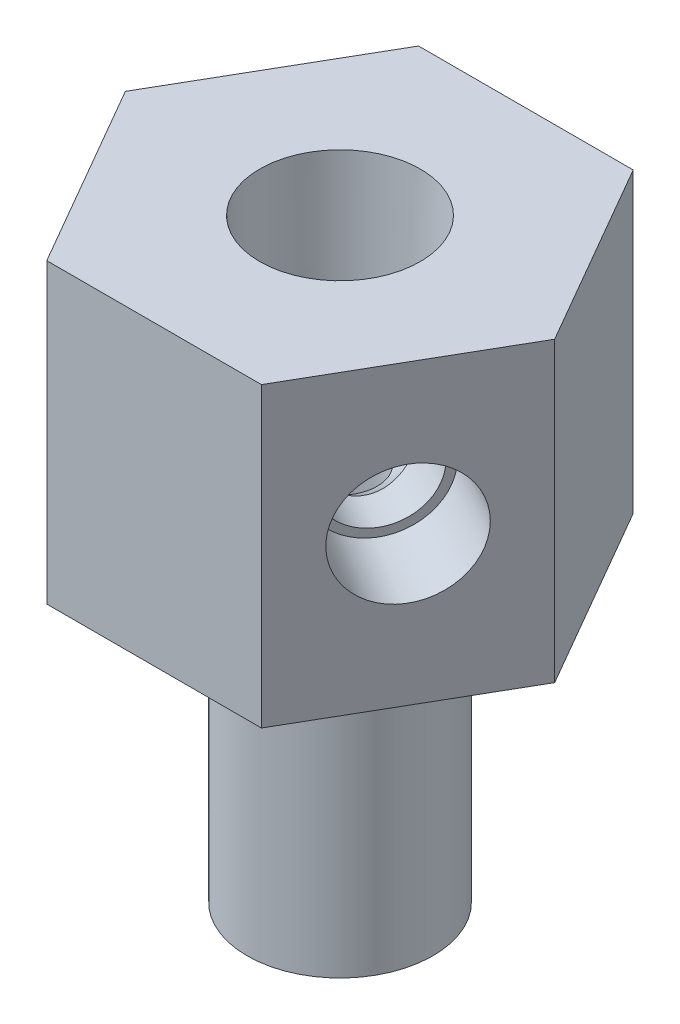
SolidWorks part; units mm, degrees
ref_plane "Front Plane" through (0, 0, 0) normal (0, 0, 1) x (1, 0, 0)
ref_plane "Top Plane" through (0, 0, 0) normal (0, 1, 0) x (1, 0, 0)
ref_plane "Right Plane" through (0, 0, 0) normal (1, 0, 0) x (0, 0, -1)
sketch "Sketch1" plane through (0, 0, 0) normal (0, 1, 0) x (1, 0, 0)
  circle A0 centre (0, 0) radius 7.9375
  dimension "D1" = 15.875
extrude "Boss-Extrude1" add sketch "Sketch1" along normal blind 25.4
cosmetic thread "Cosmetic Thread1" parameters "D2"=14.1961
sketch "Sketch2" plane through (0, 25.4, 0) normal (0, 1, 0) x (1, 0, 0)
  line L1 (18.3309, 0) -> (9.1654, 15.875)
  line L2 (9.1654, 15.875) -> (-9.1654, 15.875)
  line L3 (-9.1654, 15.875) -> (-18.3309, 0)
  line L4 (-18.3309, 0) -> (-9.1654, -15.875)
  line L5 (-9.1654, -15.875) -> (9.1654, -15.875)
  line L6 (9.1654, -15.875) -> (18.3309, 0)
  circle A0 centre (0, 0) radius 15.875 construction
  dimension "D1" = 31.75
extrude "Boss-Extrude2" add sketch "Sketch2" along normal blind 25.4
sketch "Sketch3" plane through (0, 0, 0) normal (0, -1, 0) x (1, 0, 0)
  circle A0 centre (0, 0) radius 3.175
  dimension "D1" = 6.35
extrude "Cut-Extrude1" cut sketch "Sketch3" against normal through all
sketch "Sketch6" plane through (0, 25.4, 0) normal (0, -1, 0) x (1, 0, 0)
  line L0 (-18.3309, 0) -> (-9.1654, 15.875) construction
  line L1 (-9.1654, -15.875) -> (-18.3309, 0) construction
  line L2 (9.1654, -15.875) -> (-9.1654, -15.875) construction
  line L3 (18.3309, 0) -> (9.1654, -15.875) construction
  line L4 (9.1654, 15.875) -> (18.3309, 0) construction
  line L5 (-9.1654, 15.875) -> (9.1654, 15.875) construction
  line L6 (-18.3309, 0) -> (-9.1654, 15.875)
  line L7 (-9.1654, -15.875) -> (-18.3309, 0)
  line L8 (9.1654, -15.875) -> (-9.1654, -15.875)
  line L9 (18.3309, 0) -> (9.1654, -15.875)
  line L10 (9.1654, 15.875) -> (18.3309, 0)
  line L11 (-9.1654, 15.875) -> (9.1654, 15.875)
  circle A0 centre (0, 0) radius 6.6675
  dimension "D1" = 13.335
extrude "Cut-Extrude2" cut sketch "Sketch6" along normal blind 2.3813
hole_wizard "1/4 NPT Tapped Hole1" positions "Sketch5" profile "Sketch4" size "1/4" standard "ANSI Inch"
sketch "Sketch5" plane through (0, 50.8, 0) normal (0, 1, 0) x (1, 0, 0)
  point P0 (0, 0)
sketch "Sketch4" plane through (0, 50.8, 0) normal (1, 0, 0) x (0, 0, 1)
  line L0 (0, 0) -> (0, 20.3603)
  line L1 (5.5626, 17.018) -> (0, 20.3603)
  line L2 (-5.5626, 17.018) -> (0, 20.3603) construction
  line L3 (5.5626, 17.018) -> (5.5626, 9.906)
  line L4 (5.5626, 9.906) -> (6.558, 9.906)
  line L5 (6.558, 9.906) -> (6.8546, 0)
  line L6 (-6.558, 9.906) -> (-6.8546, 0) construction
  line L7 (6.8546, 0) -> (0, 0)
  line L8 (0, -6.35) -> (0, 107.95) construction
  line L11 (-5.5626, 9.906) -> (-6.558, 9.906) construction
  dimension "Tap Drill Dia." = 11.1252
  dimension "Tap Drill Depth" = 17.018
  dimension "Thread Dia." = 13.7092
  dimension "Thread Angle" = 3.43
  dimension "Thread Depth" = 9.906
  dimension "Drill Angle" = 118
hole_wizard "1/8 NPT Tapped Hole1" positions "3DSketch1" profile "Sketch9" size "1/8" standard "ANSI Inch"
sketch3d "3DSketch1"
  line L0 (9.1654, 25.4, -15.875) -> (-9.1654, 25.4, -15.875) construction
  line L3 (-18.3309, 25.4, 0) -> (-9.1654, 25.4, 15.875) construction
  line L4 (9.1654, 25.4, 15.875) -> (18.3309, 25.4, 0) construction
  line L5 (9.1654, 50.8, -15.875) -> (9.1654, 25.4, -15.875) construction
  line L6 (9.1654, 50.8, 15.875) -> (9.1654, 25.4, 15.875) construction
  line L7 (-18.3309, 50.8, 0) -> (-18.3309, 25.4, 0) construction
  point P0 (13.7482, 38.1, 7.9374)
  point P2 (-0.0002, 38.1, -15.875)
  point P4 (-13.7481, 38.1, 7.9376)
  dimension "D1" = 12.7
  dimension "D2" = 12.7
  dimension "D3" = 12.7
  dimension "D4" = 9.1656
  dimension "D5" = 9.1656
  dimension "D6" = 9.1656
sketch "Sketch9" plane through (13.7482, 38.1, 7.9374) normal (0, 1, 0) x (0.5, 0, -0.866)
  line L0 (0, 0) -> (0, 14.2175)
  line L1 (4.2164, 11.684) -> (0, 14.2175)
  line L2 (-4.2164, 11.684) -> (0, 14.2175) construction
  line L3 (4.2164, 11.684) -> (4.2164, 6.858)
  line L4 (4.2164, 6.858) -> (4.9362, 6.858)
  line L5 (4.9362, 6.858) -> (5.1415, 0)
  line L6 (-4.9362, 6.858) -> (-5.1415, 0) construction
  line L7 (5.1415, 0) -> (0, 0)
  line L8 (0, -6.35) -> (0, 107.95) construction
  line L11 (-4.2164, 6.858) -> (-4.9362, 6.858) construction
  dimension "Tap Drill Dia." = 8.4328
  dimension "Tap Drill Depth" = 11.684
  dimension "Thread Dia." = 10.283
  dimension "Thread Angle" = 3.43
  dimension "Thread Depth" = 6.858
  dimension "Drill Angle" = 118
